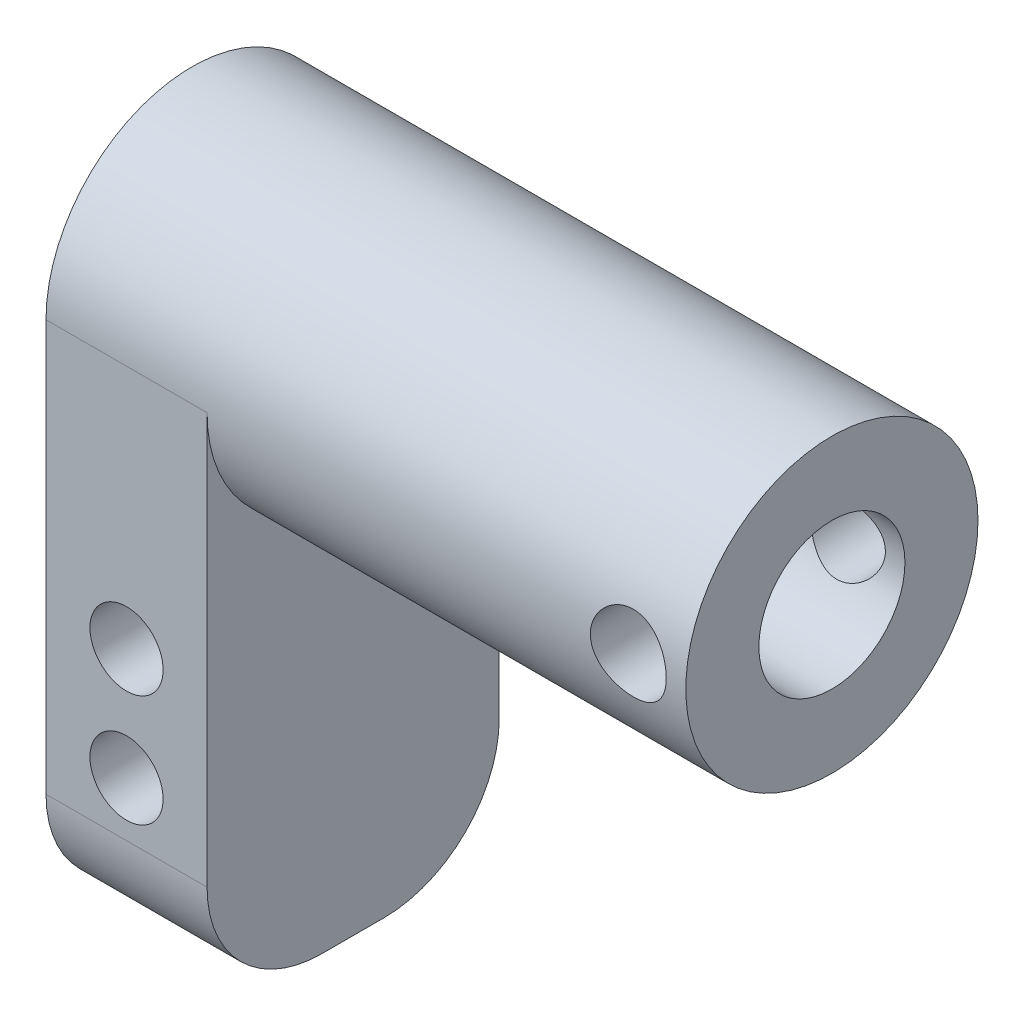
SolidWorks part; units mm, degrees
ref_plane "Front Plane" through (0, 0, 0) normal (1, 0, 0) x (0, 1, 0)
ref_plane "Top Plane" through (0, 0, 0) normal (0, 0, 1) x (0, 1, 0)
ref_plane "Right Plane" through (0, 0, 0) normal (0, 1, 0) x (-1, 0, 0)
sketch "Sketch1" plane through (0, 0, 0) normal (1, 0, 0) x (0, 1, 0)
  circle A0 centre (0, 0) radius 3.175
  circle A1 centre (0, 0) radius 3
  circle A2 centre (0, 0) radius 6.35
  dimension "D1" = 6
  dimension "D2" = 6.35
  dimension "D3" = 12.7
extrude "Boss-Extrude1" add sketch "Sketch1" along normal blind 27.81 contours A2 A0 region at (0, -6.1704, 0)
extrude "Boss-Extrude2" add sketch "Sketch1<3>" along normal blind 7 contours A0 A1 region at (0, -3.0852, 0)
sketch "Sketch1<3>" plane through (0, 0, 0) normal (1, 0, 0) x (0, 1, 0) same geometry as "Sketch1"
ref_plane "Plane1" through (0, 0, 6.35) normal (0, 0, 1) x (0, 1, 0)
sketch "Sketch7" plane through (0, 0, 6.35) normal (0, 0, 1) x (0, 1, 0)
  line L2 (-6.35, -27.81) -> (6.35, -27.81) construction
  circle A0 centre (0, -25.31) radius 1.0922
  point P0 (0, -25.31)
  dimension "D2" = 2.1844
  dimension "D1" = 2.5
hole_wizard "M4x0.7 Tapped Hole1" positions "Sketch7" profile "Sketch9" tap size "M4x0.7" standard "ANSI Metric" end condition through all
sketch "Sketch9" plane through (25.31, 0, 6.35) normal (1, 0, 0) x (0, -1, 0)
  line L0 (0, 0) -> (0, 12.7)
  line L1 (0, 12.7) -> (1.65, 12.7)
  line L2 (1.65, 12.7) -> (1.65, 0)
  line L5 (1.65, 0) -> (0, 0)
  line L11 (0, -6.35) -> (0, 107.95) construction
  dimension "Thru Tap Drill Dia." = 3.3
  dimension "Thru Tap Drill Depth" = 12.7
cosmetic thread "Hole Thread10" parameters "D2"=4
sketch "Sketch10" plane through (0, 0, 0) normal (-1, 0, 0) x (0, -1, 0)
  line L0 (0, 6.35) -> (22.86, 6.35)
  line L1 (15.2955, 6.35) -> (-15.2955, 6.35) construction
  line L2 (22.86, 6.35) -> (22.86, -6.35)
  line L3 (22.86, -6.35) -> (0, -6.35)
  circle A0 centre (0, 0) radius 6.35 construction
  arc A1 (-1.65, -6.1319) -> (1.65, -6.1319) centre (0, 0) ccw construction
  arc A2 (0, 6.35) -> (0, -6.35) centre (0, 0) cw
  dimension "D1" = 22.86
extrude "Boss-Extrude3" add sketch "Sketch10" against normal blind 7 contours L0 A2 L3 L2 region at (0, -13.8674, 0)
fillet "Fillet2" radius 5 2 edges at (3.5, -22.86, 6.35) (3.5, -22.86, -6.35)
sketch "Sketch11" plane through (0, 0, -6.35) normal (0, 0, -1) x (1, 0, 0)
  line L0 (0, 0) -> (27.81, 0) construction
  line L1 (27.81, -6.35) -> (27.81, 6.35) construction
  line L2 (3.5, 17.86) -> (3.5, 0) construction
  line L3 (7, 17.86) -> (0, 17.86) construction
  circle A0 centre (3.5, 15.5) radius 1.59
  circle A1 centre (3.5, 10.64) radius 1.59
  point P7 (3.5, 15.3122)
  point P10 (3.5, 9.5426)
  point P15 (3.5, 15.5)
  point P16 (0, 0)
  point P17 (0, 0)
  dimension "D3" = 3.18
  dimension "D4" = 3.18
  dimension "D1" = 10.64
  dimension "D2" = 4.86
extrude "Cut-Extrude5" cut sketch "Sketch11" against normal through all
sketch "Sketch14" plane through (0, 0, 0) normal (-1, 0, 0) x (0, 0, 1)
  line L0 (0.5112, -3.2591) -> (0.3942, -3.8443)
  line L1 (0, 0) -> (0, -3.9) construction
  line L2 (0, 0) -> (0.5602, -3.2689) construction
  line L3 (0.6032, -3.2433) -> (0.9083, -3.7562)
  line L4 (-0.6343, -3.2373) -> (-0.9444, -3.7473)
  line L5 (-0.5425, -3.254) -> (-0.4312, -3.8403)
  line L6 (-1.7033, -2.8251) -> (-2.1691, -3.1983)
  line L7 (-1.6227, -2.8722) -> (-1.7186, -3.4613)
  line L8 (-2.5669, -2.0722) -> (-3.1322, -2.2635)
  line L9 (-2.5072, -2.144) -> (-2.7988, -2.6647)
  line L10 (-3.1208, -1.0693) -> (-3.7174, -1.0558)
  line L11 (-3.0893, -1.1572) -> (-3.5414, -1.5468)
  line L12 (-3.2983, 0.0625) -> (-3.8543, 0.2793)
  line L13 (-3.2988, -0.0308) -> (-3.8569, -0.2422)
  line L14 (-3.078, 1.1869) -> (-3.5264, 1.5808)
  line L15 (-3.1104, 1.0993) -> (-3.7071, 1.0915)
  line L16 (-2.4865, 2.168) -> (-2.773, 2.6915)
  line L17 (-2.5468, 2.0968) -> (-3.1102, 2.2936)
  line L18 (-1.595, 2.8877) -> (-1.6852, 3.4776)
  line L19 (-1.6761, 2.8414) -> (-2.1382, 3.219)
  line L20 (-0.5112, 3.2591) -> (-0.3942, 3.8443)
  line L21 (-0.6032, 3.2433) -> (-0.9083, 3.7562)
  line L22 (0.6343, 3.2373) -> (0.9444, 3.7473)
  line L23 (0.5425, 3.254) -> (0.4312, 3.8403)
  line L24 (1.7033, 2.8251) -> (2.1691, 3.1983)
  line L25 (1.6227, 2.8722) -> (1.7186, 3.4613)
  line L26 (2.5669, 2.0722) -> (3.1322, 2.2635)
  line L27 (2.5072, 2.144) -> (2.7988, 2.6647)
  line L28 (3.1208, 1.0693) -> (3.7174, 1.0558)
  line L29 (3.0893, 1.1572) -> (3.5414, 1.5468)
  line L30 (3.2983, -0.0625) -> (3.8543, -0.2793)
  line L31 (3.2988, 0.0308) -> (3.8569, 0.2422)
  line L32 (3.078, -1.1869) -> (3.5264, -1.5808)
  line L33 (3.1104, -1.0993) -> (3.7071, -1.0915)
  line L34 (2.4865, -2.168) -> (2.773, -2.6915)
  line L35 (2.5468, -2.0968) -> (3.1102, -2.2936)
  line L36 (1.595, -2.8877) -> (1.6852, -3.4776)
  line L37 (1.6761, -2.8414) -> (2.1382, -3.219)
  line L38 (-0.0375, -3.8998) -> (0, -3.9)
  line L39 (-1.3691, -3.6518) -> (-1.3339, -3.6648)
  line L40 (-2.5355, -2.9633) -> (-2.5069, -2.9876)
  line L41 (-3.3775, -1.95) -> (-3.3961, -1.9174)
  line L42 (-3.8408, -0.6772) -> (-3.8471, -0.6402)
  line L43 (-3.8408, 0.6772) -> (-3.8341, 0.7142)
  line L44 (-3.3775, 1.95) -> (-3.3586, 1.9824)
  line L45 (-2.5069, 2.9876) -> (-2.478, 3.0116)
  line L46 (-1.3339, 3.6648) -> (-1.2985, 3.6775)
  line L47 (0, 3.9) -> (0.0375, 3.8998)
  line L48 (1.3339, 3.6648) -> (1.3691, 3.6518)
  line L49 (2.5069, 2.9876) -> (2.5355, 2.9633)
  line L50 (3.3775, 1.95) -> (3.3961, 1.9174)
  line L51 (3.8408, 0.6772) -> (3.8471, 0.6402)
  line L52 (3.8408, -0.6772) -> (3.8341, -0.7142)
  line L53 (3.3775, -1.95) -> (3.3586, -1.9824)
  line L54 (2.5069, -2.9876) -> (2.478, -3.0116)
  line L55 (1.3339, -3.6648) -> (1.2985, -3.6775)
  arc A0 (0.3496, -3.8843) -> (0, -3.9) centre (0, 0) cw
  arc A1 (0.3496, -3.8843) -> (0.3942, -3.8443) centre (0.3452, -3.8345) ccw
  arc A2 (0.5112, -3.2591) -> (0.6032, -3.2433) centre (0.5602, -3.2689) cw
  arc A3 (0.4199, -3.8983) -> (0.3942, -3.8443) centre (0.4432, -3.8541) cw
  arc A4 (0.4199, -3.8983) -> (0.7367, -4.0472) centre (2.2357, -0.4468) ccw
  arc A6 (0.9636, -3.7791) -> (0.9083, -3.7562) centre (0.9513, -3.7306) cw
  arc A7 (0.9636, -3.7791) -> (1.2985, -3.6775) centre (0, 0) ccw
  arc A8 (-0.9999, -3.7696) -> (-1.3339, -3.6648) centre (0, 0) cw
  arc A9 (-0.9999, -3.7696) -> (-0.9444, -3.7473) centre (-0.9871, -3.7213) ccw
  arc A10 (-0.6343, -3.2373) -> (-0.5425, -3.254) centre (-0.5916, -3.2633) cw
  arc A11 (-0.387, -3.8808) -> (-0.4312, -3.8403) centre (-0.3821, -3.831) cw
  arc A12 (-0.387, -3.8808) -> (-0.0375, -3.8998) centre (0, 0) ccw
  arc A13 (-2.2289, -3.2003) -> (-2.5069, -2.9876) centre (0, 0) cw
  arc A14 (-2.2289, -3.2003) -> (-2.1691, -3.1983) centre (-2.2004, -3.1593) ccw
  arc A15 (-1.7033, -2.8251) -> (-1.6227, -2.8722) centre (-1.6721, -2.8642) cw
  arc A16 (-1.691, -3.5143) -> (-1.7186, -3.4613) centre (-1.6693, -3.4693) cw
  arc A17 (-1.691, -3.5143) -> (-1.3691, -3.6518) centre (0, 0) ccw
  arc A18 (-3.1891, -2.245) -> (-3.3775, -1.95) centre (0, 0) cw
  arc A19 (-3.1891, -2.245) -> (-3.1322, -2.2635) centre (-3.1482, -2.2162) ccw
  arc A20 (-2.5669, -2.0722) -> (-2.5072, -2.144) centre (-2.5508, -2.1196) cw
  arc A21 (-2.791, -2.7241) -> (-2.7988, -2.6647) centre (-2.7552, -2.6891) cw
  arc A22 (-2.791, -2.7241) -> (-2.5355, -2.9633) centre (0, 0) ccw
  arc A23 (-3.7646, -1.0188) -> (-3.8408, -0.6772) centre (0, 0) cw
  arc A24 (-3.7646, -1.0188) -> (-3.7174, -1.0558) centre (-3.7163, -1.0058) ccw
  arc A25 (-3.1208, -1.0693) -> (-3.0893, -1.1572) centre (-3.1219, -1.1193) cw
  arc A26 (-3.5543, -1.6052) -> (-3.5414, -1.5468) centre (-3.5088, -1.5846) cw
  arc A27 (-3.5543, -1.6052) -> (-3.3961, -1.9174) centre (0, 0) ccw
  arc A28 (-3.886, 0.3302) -> (-3.8408, 0.6772) centre (0, 0) cw
  arc A29 (-3.886, 0.3302) -> (-3.8543, 0.2793) centre (-3.8362, 0.3259) ccw
  arc A30 (-3.2983, 0.0625) -> (-3.2988, -0.0308) centre (-3.3165, 0.016) cw
  arc A31 (-3.889, -0.2928) -> (-3.8569, -0.2422) centre (-3.8391, -0.289) cw
  arc A32 (-3.889, -0.2928) -> (-3.8471, -0.6402) centre (0, 0) ccw
  arc A33 (-3.5387, 1.6393) -> (-3.3775, 1.95) centre (0, 0) cw
  arc A34 (-3.5387, 1.6393) -> (-3.5264, 1.5808) centre (-3.4934, 1.6183) ccw
  arc A35 (-3.078, 1.1869) -> (-3.1104, 1.0993) centre (-3.111, 1.1493) cw
  arc A36 (-3.7546, 1.055) -> (-3.7071, 1.0915) centre (-3.7065, 1.0415) cw
  arc A37 (-3.7546, 1.055) -> (-3.8341, 0.7142) centre (0, 0) ccw
  arc A38 (-2.7646, 2.7508) -> (-2.5069, 2.9876) centre (0, 0) cw
  arc A39 (-2.7646, 2.7508) -> (-2.773, 2.6915) centre (-2.7292, 2.7155) ccw
  arc A40 (-2.4865, 2.168) -> (-2.5468, 2.0968) centre (-2.5303, 2.144) cw
  arc A41 (-3.1673, 2.2755) -> (-3.1102, 2.2936) centre (-3.1267, 2.2464) cw
  arc A42 (-3.1673, 2.2755) -> (-3.3586, 1.9824) centre (0, 0) ccw
  arc A43 (-1.6571, 3.5305) -> (-1.3339, 3.6648) centre (0, 0) cw
  arc A44 (-1.6571, 3.5305) -> (-1.6852, 3.4776) centre (-1.6358, 3.4852) ccw
  arc A45 (-1.595, 2.8877) -> (-1.6761, 2.8414) centre (-1.6444, 2.8801) cw
  arc A46 (-2.198, 3.2216) -> (-2.1382, 3.219) centre (-2.1698, 3.1803) cw
  arc A47 (-2.198, 3.2216) -> (-2.478, 3.0116) centre (0, 0) ccw
  arc A48 (-0.3496, 3.8843) -> (0, 3.9) centre (0, 0) cw
  arc A49 (-0.3496, 3.8843) -> (-0.3942, 3.8443) centre (-0.3452, 3.8345) ccw
  arc A50 (-0.5112, 3.2591) -> (-0.6032, 3.2433) centre (-0.5602, 3.2689) cw
  arc A51 (-0.9636, 3.7791) -> (-0.9083, 3.7562) centre (-0.9513, 3.7306) cw
  arc A52 (-0.9636, 3.7791) -> (-1.2985, 3.6775) centre (0, 0) ccw
  arc A53 (0.9999, 3.7696) -> (1.3339, 3.6648) centre (0, 0) cw
  arc A54 (0.9999, 3.7696) -> (0.9444, 3.7473) centre (0.9871, 3.7213) ccw
  arc A55 (0.6343, 3.2373) -> (0.5425, 3.254) centre (0.5916, 3.2633) cw
  arc A56 (0.387, 3.8808) -> (0.4312, 3.8403) centre (0.3821, 3.831) cw
  arc A57 (0.387, 3.8808) -> (0.0375, 3.8998) centre (0, 0) ccw
  arc A58 (2.2289, 3.2003) -> (2.5069, 2.9876) centre (0, 0) cw
  arc A59 (2.2289, 3.2003) -> (2.1691, 3.1983) centre (2.2004, 3.1593) ccw
  arc A60 (1.7033, 2.8251) -> (1.6227, 2.8722) centre (1.6721, 2.8642) cw
  arc A61 (1.691, 3.5143) -> (1.7186, 3.4613) centre (1.6693, 3.4693) cw
  arc A62 (1.691, 3.5143) -> (1.3691, 3.6518) centre (0, 0) ccw
  arc A63 (3.1891, 2.245) -> (3.3775, 1.95) centre (0, 0) cw
  arc A64 (3.1891, 2.245) -> (3.1322, 2.2635) centre (3.1482, 2.2162) ccw
  arc A65 (2.5669, 2.0722) -> (2.5072, 2.144) centre (2.5508, 2.1196) cw
  arc A66 (2.791, 2.7241) -> (2.7988, 2.6647) centre (2.7552, 2.6891) cw
  arc A67 (2.791, 2.7241) -> (2.5355, 2.9633) centre (0, 0) ccw
  arc A68 (3.7646, 1.0188) -> (3.8408, 0.6772) centre (0, 0) cw
  arc A69 (3.7646, 1.0188) -> (3.7174, 1.0558) centre (3.7163, 1.0058) ccw
  arc A70 (3.1208, 1.0693) -> (3.0893, 1.1572) centre (3.1219, 1.1193) cw
  arc A71 (3.5543, 1.6052) -> (3.5414, 1.5468) centre (3.5088, 1.5846) cw
  arc A72 (3.5543, 1.6052) -> (3.3961, 1.9174) centre (0, 0) ccw
  arc A73 (3.886, -0.3302) -> (3.8408, -0.6772) centre (0, 0) cw
  arc A74 (3.886, -0.3302) -> (3.8543, -0.2793) centre (3.8362, -0.3259) ccw
  arc A75 (3.2983, -0.0625) -> (3.2988, 0.0308) centre (3.3165, -0.016) cw
  arc A76 (3.889, 0.2928) -> (3.8569, 0.2422) centre (3.8391, 0.289) cw
  arc A77 (3.889, 0.2928) -> (3.8471, 0.6402) centre (0, 0) ccw
  arc A78 (3.5387, -1.6393) -> (3.3775, -1.95) centre (0, 0) cw
  arc A79 (3.5387, -1.6393) -> (3.5264, -1.5808) centre (3.4934, -1.6183) ccw
  arc A80 (3.078, -1.1869) -> (3.1104, -1.0993) centre (3.111, -1.1493) cw
  arc A81 (3.7546, -1.055) -> (3.7071, -1.0915) centre (3.7065, -1.0415) cw
  arc A82 (3.7546, -1.055) -> (3.8341, -0.7142) centre (0, 0) ccw
  arc A83 (2.7646, -2.7508) -> (2.5069, -2.9876) centre (0, 0) cw
  arc A84 (2.7646, -2.7508) -> (2.773, -2.6915) centre (2.7292, -2.7155) ccw
  arc A85 (2.4865, -2.168) -> (2.5468, -2.0968) centre (2.5303, -2.144) cw
  arc A86 (3.1673, -2.2755) -> (3.1102, -2.2936) centre (3.1267, -2.2464) cw
  arc A87 (3.1673, -2.2755) -> (3.3586, -1.9824) centre (0, 0) ccw
  arc A88 (1.6571, -3.5305) -> (1.3339, -3.6648) centre (0, 0) cw
  arc A89 (1.6571, -3.5305) -> (1.6852, -3.4776) centre (1.6358, -3.4852) ccw
  arc A90 (1.595, -2.8877) -> (1.6761, -2.8414) centre (1.6444, -2.8801) cw
  arc A91 (2.198, -3.2216) -> (2.1382, -3.219) centre (2.1698, -3.1803) cw
  arc A92 (2.198, -3.2216) -> (2.478, -3.0116) centre (0, 0) ccw
  point P207 (0, 0)
  dimension "D1" = 3.9
  dimension "D2" = 0.05
  dimension "D3" = 0.05
  dimension "D4" = 0.04
  dimension "D5" = 18
  dimension "D6" = 0.5968
  dimension "D8" = 0.35
extrude "Cut-Extrude6" cut sketch "Sketch14" against normal blind 15 contours A91 A92 L54 A83 A84 L34 A85 L35 A86 A87 L53 A78 A79 L32 A80 L33 A81 A82 L52 A73 A74 L30 A75 L31 A76 A77 L51 A68 A69 L28 A70 L29 A71 A72 L50 A63 A64 L26 A65 L27 A66 A67 L49 A58 A59 L24 A60 L25 A61 A62 L48 region at (0, 0, 0)
